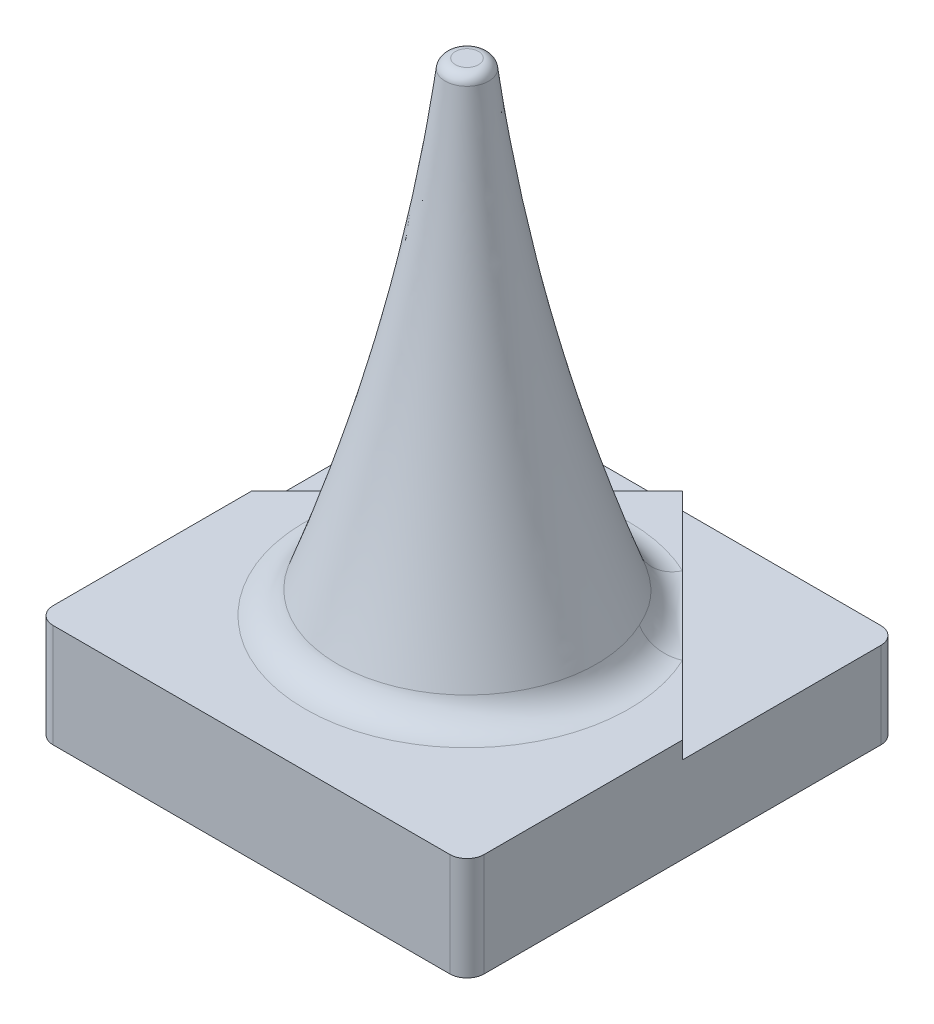
SolidWorks part; units mm, degrees
ref_plane "Plan de face" through (0, 0, 0) normal (0, 0, 1) x (1, 0, 0)
ref_plane "Plan de dessus" through (0, 0, 0) normal (0, 1, 0) x (1, 0, 0)
ref_plane "Plan de droite" through (0, 0, 0) normal (1, 0, 0) x (0, 0, -1)
sketch "Esquisse1" plane through (0, 0, 0) normal (0, 1, 0) x (1, 0, 0)
  line L1 (-6.25, -6.25) -> (6.25, -6.25)
  line L2 (-6.25, -6.25) -> (-6.25, 6.25)
  line L3 (-6.25, 6.25) -> (6.25, 6.25)
  line L4 (6.25, -6.25) -> (6.25, 6.25)
  line L5 (-6.25, -6.25) -> (6.25, 6.25) construction
  line L6 (-6.25, 6.25) -> (6.25, -6.25) construction
  point P0 (0, 0)
  dimension "D1" = 12.5
  dimension "D2" = 12.5
extrude "Boss.-Extru.1" add sketch "Esquisse1" along normal blind 3
sketch "Esquisse2" plane through (0, 3, 0) normal (0, 1, 0) x (1, 0, 0)
  line L0 (-6.25, 0) -> (0, 6.25)
  line L1 (-6.25, 6.25) -> (-6.25, -6.25) construction
  line L2 (6.25, 6.25) -> (-6.25, 6.25) construction
  line L3 (0, 6.25) -> (6.25, 0)
  line L4 (6.25, -6.25) -> (6.25, 6.25) construction
  line L5 (6.25, 0) -> (6.25, 6.25)
  line L6 (6.25, 6.25) -> (-6.25, 6.25)
  line L7 (-6.25, 6.25) -> (-6.25, 0)
  line M1 (6.25, -6.25) -> (6.25, 6.25)
  line M2 (6.25, 6.25) -> (-6.25, 6.25)
  line M3 (-6.25, 6.25) -> (-6.25, -6.25)
extrude "Enlèv. mat.-Extru.1" cut sketch "Esquisse2" against normal blind 0.5 contours L0 M3 M2 | L3 M2 M1 region at (-4.1667, 3, -4.1667) region at (4.1667, 3, -4.1667)
sketch "Esquisse4" plane through (0, 0, 0) normal (0, 0, 1) x (1, 0, 0)
  line L0 (-6.25, 3) -> (6.25, 3) construction
  line L1 (0, 17) -> (0, 3)
  line L2 (0, 3) -> (4, 3)
  line L3 (0.6, 17) -> (0, 17)
  spline S0 degree 2 poles (4, 3) (1.455, 9.7704) (0.6, 17) knots 0 0 0 1 1 1
  dimension "D1" = 4
  dimension "D2" = 14
  dimension "D3" = 0.6
revolve "Révolution1" add sketch "Esquisse4" angle 360 about L1
fillet "Congé2" radius 0.3 1 edges at (-0.6, 17, 0)
fillet "Congé3" radius 0.5 4 edges at (-6.25, 1.25, -6.25) (6.25, 1.25, -6.25) (6.25, 1.5, 6.25) (-6.25, 1.5, 6.25)
sketch "Esquisse5" plane through (0, 0, 0) normal (0, 0, 1) x (1, 0, 0)
  line L0 (6.25, 3) -> (6.25, 0) construction
  line L1 (0, 16) -> (0, 0)
  line L2 (0, 0) -> (4.25, 0)
  line L3 (0.4714, 16) -> (0, 16)
  line L4 (-5.75, 0) -> (5.75, 0) construction
  spline S0 degree 3 poles (4.25, 0) (2.4076, 3.8311) (0.8303, 13.1151) (0.4714, 16) knots 0 0 0 0 1 1 1 1
  dimension "D2" = 16
  dimension "D4" = 0
  dimension "D6" = 6.25
revolve "Enlèvement de matière-Révolution1" cut sketch "Esquisse5" angle 360 about L1
fillet "Congé4" radius 1 1 edges at (-4, 3, 0)
